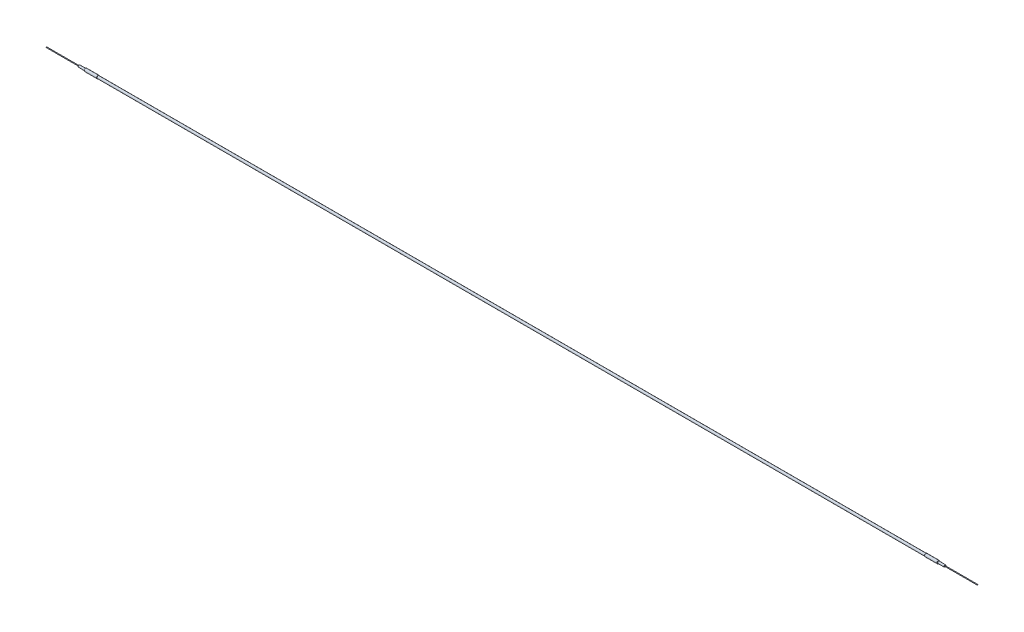
SolidWorks part; units mm, degrees
ref_plane "Front" through (0, 0, 0) normal (0, 0, 1) x (1, 0, 0)
ref_plane "Top" through (0, 0, 0) normal (0, 1, 0) x (1, 0, 0)
ref_plane "Right" through (0, 0, 0) normal (1, 0, 0) x (0, 0, -1)
sketch "Sketch3" plane through (0, 0, 0) normal (1, 0, 0) x (0, 0, -1)
  circle A0 centre (0, 0) radius 4.7625
  dimension "D1" = 9.525
extrude "Boss-Extrude1" add sketch "Sketch3" along normal blind 3230.88
sketch "Sketch4" plane through (3230.88, 0, 0) normal (1, 0, 0) x (0, 0, -1)
  circle A0 centre (0, 0) radius 5.4991
  dimension "D1" = 10.9982
extrude "Boss-Extrude2" add sketch "Sketch4" along normal blind 50.8
sketch "Sketch5" plane through (0, 0, 0) normal (-1, 0, 0) x (0, 0, 1)
  circle A0 centre (0, 0) radius 5.4991
  dimension "D1" = 10.9982
extrude "Boss-Extrude3" add sketch "Sketch5" along normal blind 50.8
sketch "Sketch6" plane through (-50.8, 0, 0) normal (-1, 0, 0) x (0, 0, 1)
  circle A0 centre (0, 0) radius 3.81
  dimension "D1" = 7.62
extrude "Boss-Extrude4" add sketch "Sketch6" along normal blind 25.4
sketch "Sketch7" plane through (3281.68, 0, 0) normal (1, 0, 0) x (0, 0, -1)
  circle A0 centre (0, 0) radius 3.81
  dimension "D1" = 7.62
extrude "Boss-Extrude5" add sketch "Sketch7" along normal blind 25.4
chamfer "Chamfer1" distance 1.27 angle 45 6 edges at (-76.2, 0, 3.81) (0, 0, 5.4991) (-50.8, 0, 5.4991) (3307.08, 0, -3.81) (3281.68, 0, -5.4991) (3230.88, 0, -5.4991)
sketch "Sketch8" plane through (-76.2, 0, 0) normal (-1, 0, 0) x (0, 0, 1)
  circle A0 centre (0, 0) radius 1.27
  dimension "D1" = 2.54
extrude "Boss-Extrude6" add sketch "Sketch8" along normal blind 127
sketch "Sketch9" plane through (3307.08, 0, 0) normal (1, 0, 0) x (0, 0, -1)
  circle A0 centre (0, 0) radius 1.27
  dimension "D1" = 2.54
extrude "Boss-Extrude7" add sketch "Sketch9" along normal blind 127
